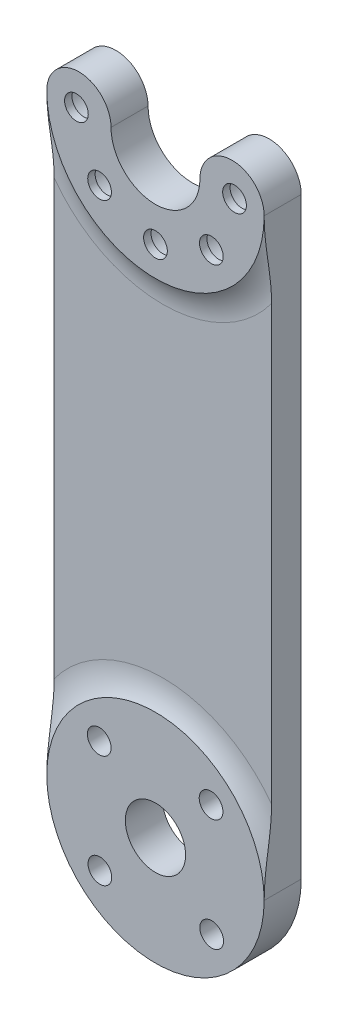
SolidWorks part; units mm, degrees
ref_plane "Plano frontal" through (0, 0, 0) normal (0, 0, 1) x (1, 0, 0)
ref_plane "Plano superior" through (0, 0, 0) normal (0, 1, 0) x (1, 0, 0)
ref_plane "Plano direito" through (0, 0, 0) normal (1, 0, 0) x (0, 0, -1)
sketch "Esboço1" plane through (0, 0, 0) normal (0, 0, 1) x (1, 0, 0)
  arc A2 (-4.5, 0) -> (4.5, 0) centre (0, 0) ccw
  arc A3 (11, 0) -> (-11, 0) centre (0, 0) cw
  arc A4 (-4, 0) -> (4, 0) centre (0, 0) ccw construction
  arc A5 (11, 0) -> (4.5, 0) centre (7.75, 0) ccw
  arc A6 (-4.5, 0) -> (-11, 0) centre (-7.75, 0) ccw
  arc A9 (-11, 0) -> (11, 0) centre (0, 0) ccw construction
  dimension "D1" = 0.5
extrude "Ressalto-extrusão1" add sketch "Esboço1" against normal offset from surface (0.75 mm away) 2 offset beyond the face yes
sketch "Esboço3" plane through (0, 0, -0.75) normal (0, 0, -1) x (-1, 0, 0)
  line L0 (-11, 0) -> (-11, -60)
  line L2 (11, -60) -> (11, 0)
  arc A0 (11, 0) -> (4.5, 0) centre (7.75, 0) ccw construction
  arc A1 (-4.5, 0) -> (4.5, 0) centre (0, 0) ccw construction
  arc A2 (-4.5, 0) -> (-11, 0) centre (-7.75, 0) ccw construction
  arc A3 (11, 0) -> (4.5, 0) centre (7.75, 0) ccw
  arc A4 (-4.5, 0) -> (4.5, 0) centre (0, 0) ccw
  arc A5 (-4.5, 0) -> (-11, 0) centre (-7.75, 0) ccw
  arc A9 (-11, -60) -> (11, -60) centre (0, -60) ccw
extrude "Ressalto-extrusão2" add sketch "Esboço3" along normal blind 3
hole_wizard "Rebaixo para SHCS M21" positions "Sketch1" profile "Sketch2" counterbore size "M2" standard "Ansi Metric" end condition up to next
sketch "Sketch1" plane through (0, 0, -3.75) normal (0, 0, -1) x (-1, 0, 0)
  line L0 (0, 0) -> (-8, 0) construction
  line L1 (0, 0) -> (-5.6569, -5.6569) construction
  line L2 (0, 0) -> (0, -8) construction
  line L3 (0, 0) -> (5.6569, -5.6569) construction
  line L4 (0, 0) -> (8, 0) construction
  arc A0 (-9, 0) -> (-7, 0) centre (-8, 0) ccw construction
  point P0 (-8, 0)
  point P16 (-5.6569, -5.6569)
  point P18 (0, -8)
  point P20 (5.6569, -5.6569)
  point P22 (8, 0)
  dimension "D1" = 5
sketch "Sketch2" plane through (8, 0, -3.75) normal (1, 0, 0) x (0, 1, 0)
  line L0 (0, 0) -> (0, 3.75)
  line L1 (0, 3.75) -> (1.2, 3.75)
  line L3 (1.2, 3.75) -> (1.2, 3)
  line L4 (1.2, 3) -> (2.2, 3)
  line L5 (2.2, 3) -> (2.2, 0)
  line L7 (2.2, 0) -> (0, 0)
  line L11 (0, -6.35) -> (0, 107.95) construction
  dimension "Thru Hole Dia." = 2.4
  dimension "Thru Hole Depth" = 3.75
  dimension "C'Bore Dia." = 4.4
  dimension "C'Bore Depth" = 3
sketch "Esboço4" plane through (0, 0, -0.75) normal (0, 0, 1) x (1, 0, 0)
  circle A0 centre (0, -60) radius 11
  arc A1 (-11, -60) -> (11, -60) centre (0, -60) ccw construction
extrude "Ressalto-extrusão3" add sketch "Esboço4" along normal up to surface (0.75 mm away)
sketch "Esboço5" plane through (0, 0, -3.75) normal (0, 0, -1) x (-1, 0, 0)
  circle A0 centre (0, -60) radius 3.05 construction
  circle A1 centre (0, -60) radius 3.05
extrude "Corte-extrusão1" cut sketch "Esboço5" against normal through all
hole_wizard "Rebaixo para parafuso com cabeça redonda de M21" positions "Esboço6" profile "Esboço7" counterbore size "M2" standard "DIN" end condition up to next
sketch "Esboço6" plane through (0, 0, -3.75) normal (0, 0, -1) x (-1, 0, 0)
  circle A0 centre (5.6247, -65.6888) radius 0.8 construction
  point P0 (5.6247, -65.6888)
sketch "Esboço7" plane through (-5.6247, -65.6888, -3.75) normal (1, 0, 0) x (0, 1, 0)
  line L0 (0, 0) -> (0, 3.75)
  line L1 (0, 3.75) -> (1.2, 3.75)
  line L3 (1.2, 3.75) -> (1.2, 1.4)
  line L4 (1.2, 1.4) -> (2.2, 1.4)
  line L5 (2.2, 1.4) -> (2.2, 0)
  line L7 (2.2, 0) -> (0, 0)
  line L11 (0, -6.35) -> (0, 107.95) construction
  dimension "Thru Hole Dia." = 2.4
  dimension "Thru Hole Depth" = 3.75
  dimension "C'Bore Dia." = 4.4
  dimension "C'Bore Depth" = 1.4
pattern_circular "PadrãoCircular1" count 4 over 360 about axis through (0, -60, -3.75) along (0, 0, -1) of "Rebaixo para parafuso com cabeça redonda de M21"
fillet "Filete1" radius 5 2 edges at (0, -49, -0.75) (0, -11, -0.75)
